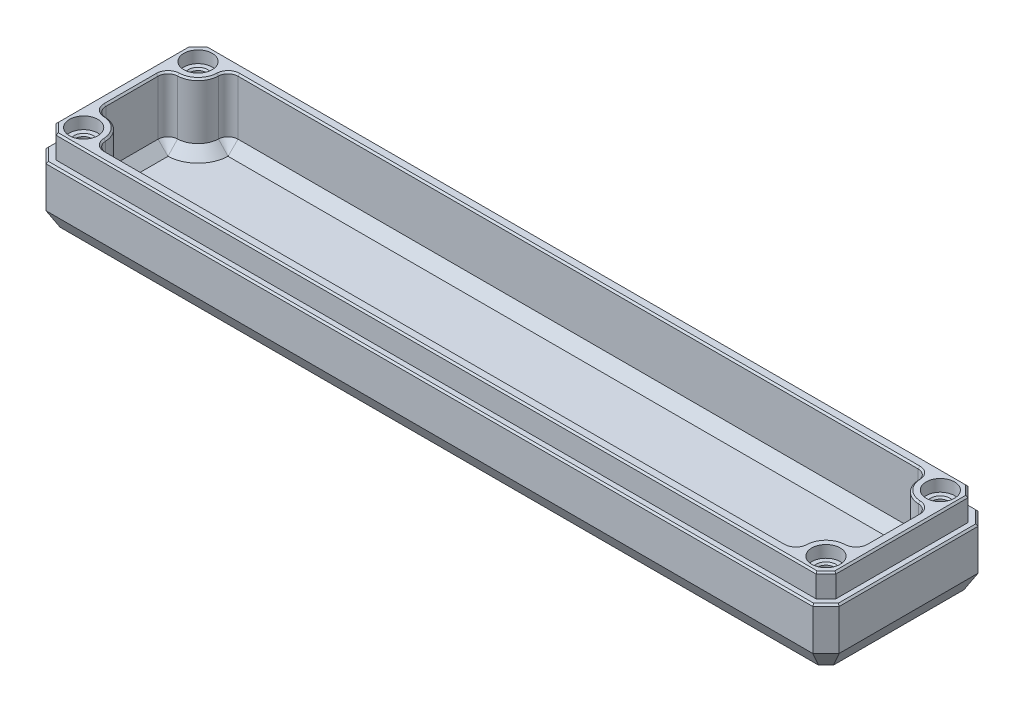
SolidWorks part; units mm, degrees
ref_plane "Front Plane" through (0, 0, 0) normal (0, 0, 1) x (1, 0, 0)
ref_plane "Top Plane" through (0, 0, 0) normal (0, 1, 0) x (1, 0, 0)
ref_plane "Right Plane" through (0, 0, 0) normal (1, 0, 0) x (0, 0, -1)
sketch "Sketch1" plane through (0, 0, 0) normal (0, 1, 0) x (1, 0, 0)
  line L0 (98.96, 31.66) -> (0, 31.66) construction
  line L1 (0, 0) -> (230, 0)
  line L2 (0, 0) -> (0, 40)
  line L3 (0, 40) -> (230, 40)
  line L4 (230, 0) -> (230, 40)
  line L5 (260, 0) -> (260, 40) construction
  line L10 (-5, 45) -> (235, 45)
  line L11 (-5, 45) -> (-5, -5)
  line L12 (-5, -5) -> (235, -5)
  line L13 (235, 45) -> (235, -5)
  line L14 (260, 20) -> (-5, 20) construction
  dimension "D3" = 5
  dimension "D4" = 5
  dimension "D5" = 5
  dimension "D1" = 40
  dimension "D2" = 230
  dimension "D6" = 5
  dimension "D7" = 30
extrude "Boss-Extrude1" add sketch "Sketch1" against normal blind 25 contours L11 L10 L13 L12
sketch "Sketch6" plane through (0, 0, 0) normal (0, 1, 0) x (1, 0, 0)
  line L1 (-3, 43) -> (233, 43)
  line L2 (-3, 43) -> (-3, -3)
  line L3 (-3, -3) -> (233, -3)
  line L4 (233, 43) -> (233, -3)
  line L5 (-5, 45) -> (235, 45) construction
  line L6 (-5, 45) -> (-5, -5) construction
  line L7 (235, 45) -> (235, -5) construction
  line L8 (-5, -5) -> (235, -5) construction
  circle A0 centre (2.7, 37.3) radius 4.3
  circle A1 centre (227.3, 37.3) radius 4.3
  circle A2 centre (227.3, 2.7) radius 4.3
  circle A3 centre (2.7, 2.7) radius 4.3
  point P4 (2.7, 41.6)
  point P5 (-1.6, 37.3)
  point P6 (227.3, 41.6)
  point P7 (231.6, 37.3)
  point P18 (231.6, 41.6)
  point P19 (-1.6, 41.6)
  point P20 (227.3, -1.6)
  point P21 (231.6, -1.6)
  point P28 (231.6, 2.7)
  point P29 (2.7, -1.6)
  point P30 (-1.6, 2.7)
  point P31 (-1.6, -1.6)
  dimension "D5" = 8.6
  dimension "D1" = 2
  dimension "D2" = 2
  dimension "D3" = 2
  dimension "D4" = 2
  dimension "D6" = 1.4
  dimension "D7" = 1.4
  dimension "D12" = 1.4
  dimension "D13" = 1.4
  dimension "D10" = 1.4
  dimension "D11" = 1.4
  dimension "D8" = 1.4
  dimension "D9" = 1.4
extrude "Cut-Extrude3" cut sketch "Sketch6" against normal blind 7 from surface flip side to cut contours L4 L3 L2 L1 starting at face at (115, 0, -20)
chamfer "Chamfer6" distance 3 angle 45 4 edges at (233, -3.5, 3) (233, -3.5, -43) (-3, -3.5, -43) (-3, -3.5, 3)
chamfer "Chamfer5" distance 4 angle 45 4 edges at (235, -16, 5) (-5, -16, 5) (-5, -16, -45) (235, -16, -45)
extrude "Cut-Extrude5" cut sketch "Sketch6<9>" against normal blind 3.6 flip side to cut
sketch "Sketch6<9>" plane through (0, 0, 0) normal (0, 1, 0) x (1, 0, 0) same geometry as "Sketch6"
sketch "Sketch16" plane through (0, -3.6, 0) normal (0, 1, 0) x (1, 0, 0)
  circle A4 centre (2.7, 2.7) radius 2.45
  circle A5 centre (2.7, 37.3) radius 2.45
  circle A6 centre (227.3, 37.3) radius 2.45
  circle A7 centre (227.3, 2.7) radius 2.45
  dimension "D1" = 4.9
extrude "Cut-Extrude10" cut sketch "Sketch16" against normal blind 16
chamfer "Chamfer8" distance 0.5 angle 45 4 edges at (2.7, -3.6, -34.85) (2.7, -3.6, -0.25) (227.3, -3.6, -0.25) (227.3, -3.6, -34.85)
ref_axis "Axis1" through (-5, -42.5921, 5) along (0, 1, 0)
chamfer "Chamfer9" distance 3 angle 60 8 edges at (-3, -25, 3) (115, -25, 5) (233, -25, 3) (235, -25, -20) (233, -25, -43) (115, -25, -45) (-3, -25, -43) (-5, -25, -20) first distance on face at (115, -25, -20)
chamfer "Chamfer11" distance 0.5 angle 45 8 edges at (231.5, 0, 1.5) (233, 0, -20) (231.5, 0, -41.5) (115, 0, -43) (-1.5, 0, -41.5) (-3, 0, -20) (-1.5, 0, 1.5) (115, 0, 3)
ref_axis "Axis2" through (-5, -7, -41) along (0, -1, 0)
chamfer "Chamfer12" distance 0.5 angle 45 8 edges at (-3, -7, -43) (-5, -7, -20) (-3, -7, 3) (115, -7, 5) (233, -7, 3) (235, -7, -20) (233, -7, -43) (115, -7, -45)
sketch "Sketch18" plane through (0, 0, 0) normal (0, 1, 0) x (1, 0, 0)
  line L0 (230, 12.0929) -> (230, 27.9071)
  line L1 (232.5, 0.2071) -> (232.5, 39.7929) construction
  line L2 (-2.5, 7) -> (232.5, 7) construction
  line L3 (0.2071, -2.5) -> (229.7929, -2.5) construction
  line L4 (-2.5, 39.7929) -> (-2.5, 0.2071) construction
  line L5 (232.5, 33) -> (-2.5, 33) construction
  line L6 (229.7929, 42.5) -> (0.2071, 42.5) construction
  line L7 (0, 12.0929) -> (0, 27.9071)
  line L8 (223, 42.5) -> (223, -2.5) construction
  line L9 (7, -2.5) -> (7, 42.5) construction
  line L10 (217.9071, 40) -> (12.0929, 40)
  line L11 (217.9071, 0) -> (12.0929, 0)
  line L12 (232.5, 8.5) -> (223, 8.5) construction
  line L13 (221.5, 7) -> (221.5, -2.5) construction
  line L14 (8.5, -2.5) -> (8.5, 7) construction
  line L15 (7, 8.5) -> (-2.5, 8.5) construction
  line L16 (232.5, 31.5) -> (223, 31.5) construction
  line L17 (221.5, 42.5) -> (221.5, 33) construction
  line L18 (8.5, 33) -> (8.5, 42.5) construction
  line L19 (7, 31.5) -> (-2.5, 31.5) construction
  circle A0 centre (227.3, 2.7) radius 4.3 construction
  circle A1 centre (227.3, 37.3) radius 4.3 construction
  circle A2 centre (2.7, 2.7) radius 4.3 construction
  circle A3 centre (2.7, 37.3) radius 6.3977 construction
  circle A4 centre (2.7, 37.3) radius 2.45 construction
  arc A5 (12.0929, 40) -> (9.0944, 37.0958) centre (12.0929, 37) ccw
  circle A6 centre (227.3, 37.3) radius 6.3977 construction
  circle A7 centre (227.3, 2.7) radius 2.45 construction
  circle A8 centre (2.7, 2.7) radius 6.3977 construction
  arc A9 (2.9042, 30.9056) -> (9.0944, 37.0958) centre (2.7, 37.3) ccw
  arc A10 (227.0958, 30.9056) -> (220.9056, 37.0958) centre (227.3, 37.3) cw
  arc A11 (220.9056, 2.9042) -> (227.0958, 9.0944) centre (227.3, 2.7) cw
  arc A12 (2.9042, 9.0944) -> (9.0944, 2.9042) centre (2.7, 2.7) cw
  arc A13 (230, 27.9071) -> (227.0958, 30.9056) centre (227, 27.9071) ccw
  arc A14 (217.9071, 0) -> (220.9056, 2.9042) centre (217.9071, 3) ccw
  arc A15 (9.0944, 2.9042) -> (12.0929, 0) centre (12.0929, 3) ccw
  arc A16 (0, 12.0929) -> (2.9042, 9.0944) centre (3, 12.0929) ccw
  arc A17 (0, 27.9071) -> (2.9042, 30.9056) centre (3, 27.9071) cw
  arc A18 (220.9056, 37.0958) -> (217.9071, 40) centre (217.9071, 37) ccw
  arc A19 (230, 12.0929) -> (227.0958, 9.0944) centre (227, 12.0929) cw
  point P48 (0, 0)
  point P54 (8.4537, -0.0973)
  point P56 (230, 31.5)
  point P65 (221.5, 0)
  point P71 (0, 8.5)
  point P74 (0, 0)
  point P75 (0, 0)
  point P76 (0, 0)
  point P81 (8.5, 40)
  dimension "D12" = 3
  dimension "D13" = 3
  dimension "D14" = 3
  dimension "D1" = 2.5
  dimension "D2" = 2.5
  dimension "D3" = 2.5
  dimension "D4" = 2.5
  dimension "D5" = 1.5
  dimension "D6" = 1.5
  dimension "D7" = 1.5
  dimension "D8" = 1.5
  dimension "D9" = 1.5
  dimension "D10" = 1.5
  dimension "D11" = 1.5
extrude "Cut-Extrude11" cut sketch "Sketch18" against normal offset from surface (20 mm away) 5 up to face at (115, -25, -20)
chamfer "Chamfer13" distance 0.5 angle 45 16 edges at (0, 0, -20) (0.8451, 0, -10.0057) (0.8451, 0, -29.9943) (7.2238, 0, -7.2238) (7.2238, 0, -32.7762) (10.0057, 0, -0.8451) (10.0057, 0, -39.1549) (115, 0, 0) (115, 0, -40) (219.9943, 0, -0.8451) (219.9943, 0, -39.1549) (222.7762, 0, -7.2238) (222.7762, 0, -32.7762) (229.1549, 0, -10.0057) (229.1549, 0, -29.9943) (230, 0, -20)
chamfer "Chamfer14" distance 3 angle 45 16 edges at (230, -20, -20) (229.1549, -20, -10.0057) (222.7762, -20, -7.2238) (219.9943, -20, -0.8451) (115, -20, 0) (10.0057, -20, -0.8451) (7.2238, -20, -7.2238) (0.8451, -20, -10.0057) (0, -20, -20) (0.8451, -20, -29.9943) (7.2238, -20, -32.7762) (10.0057, -20, -39.1549) (115, -20, -40) (219.9943, -20, -39.1549) (222.7762, -20, -32.7762) (229.1549, -20, -29.9943)
equation "\"D3@Sketch1\" = \"Wall Thickness\""
equation "\"D4@Sketch1\" = \"Wall Thickness\""
equation "\"D5@Sketch1\" = \"Wall Thickness\""
equation "\"D1@Sketch1\"=40"
equation "\"D2@Sketch1\"=230"
equation "\"D1@Boss-Extrude1\"=20 + \"Wall Thickness\""
equation "\"D6@Sketch1\" = \"Wall Thickness\""
equation "\"D2@Sketch6\" = \"Female Fit Wall Thickness\""
equation "\"D1@Sketch6\" = \"Female Fit Wall Thickness\""
equation "\"D4@Sketch6\" = \"Female Fit Wall Thickness\""
equation "\"D3@Sketch6\" = \"Female Fit Wall Thickness\""
equation "\"D5@Sketch6\" = \"Screw Head Diameter\""
equation "\"D1@Cut-Extrude3\" = \"Female Fit Wall Height\""
equation "\"D1@Cut-Extrude5\" = \"Screw Head Height\""
equation "\"D1@Sketch16\" = \"Screw Tail Diameter\""
equation "\"D1@Cut-Extrude10\" = \"Screw Tail Length\""
equation "\"D6@Sketch6\" = \"Screw Clearance to Corner\""
equation "\"D7@Sketch6\" = \"Screw Clearance to Corner\""
equation "\"D12@Sketch6\" = \"Screw Clearance to Corner\""
equation "\"D13@Sketch6\" = \"Screw Clearance to Corner\""
equation "\"D10@Sketch6\" = \"Screw Clearance to Corner\""
equation "\"D11@Sketch6\" = \"Screw Clearance to Corner\""
equation "\"D8@Sketch6\" = \"Screw Clearance to Corner\""
equation "\"D9@Sketch6\" = \"Screw Clearance to Corner\""
equation "\"Fabric Tolerance\"= 1.5"
equation "\"Female Fit Wall Thickness\"= 2"
equation "\"Female Fit Wall Height\"= 7"
equation "\"Screw Head Diameter\"= 8.6"
equation "\"Screw Head Height\"= 3.6"
equation "\"Screw Tail Length\"= 16"
equation "\"Screw Tail Diameter\"= 4.9"
equation "\"Screw Clearance to Corner\"= 1.4"
equation "\"Wall Thickness\"= 5"
equation "\"Mouse X\"= 98.96"
equation "\"Mouse Y\"= 63.25"
equation "\"Mouse Z\"= 33.90"
equation "\"D1@Cut-Extrude11\"=\"Wall Thickness\""
